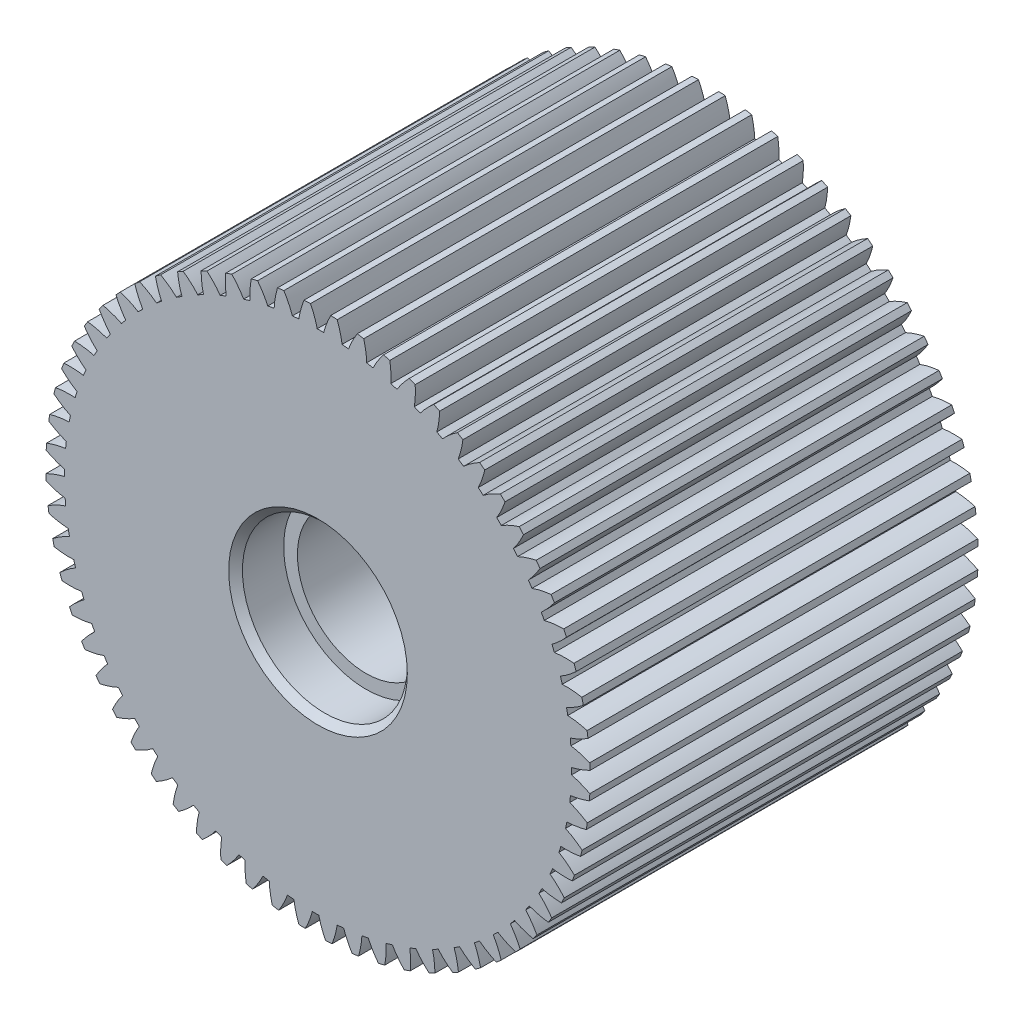
SolidWorks part; units mm, degrees
material "PLA"
ref_plane "Front Plane" through (0, 0, 0) normal (0, 0, 1) x (1, 0, 0)
ref_plane "Top Plane" through (0, 0, 0) normal (0, 1, 0) x (1, 0, 0)
ref_plane "Right Plane" through (0, 0, 0) normal (1, 0, 0) x (0, 0, -1)
sketch "Sketch1" plane through (0, 0, 0) normal (0, 0, 1) x (1, 0, 0)
  circle A0 centre (0, 0) radius 19.8
  dimension "D1" = 39.6
extrude "Boss-Extrude1" add sketch "Sketch1" along normal mid plane 28.2315
sketch "Sketch2" plane through (0, 0, 0) normal (0, 0, 1) x (1, 0, 0)
  line L0 (0, 0) -> (18.0421, 0) construction
  line L1 (0, 0) -> (19.1991, -0.1851) construction
  line L2 (0, 0) -> (18.0387, -0.3478) construction
  line L3 (18.0421, 0) -> (18.45, 0)
  line L4 (18.0387, -0.3478) -> (18.4466, -0.3557)
  circle A0 centre (0, 0) radius 19.2 construction
  circle A1 centre (0, 0) radius 18.0421 construction
  circle A2 centre (0, 0) radius 18.45
  circle A3 centre (0, 0) radius 19.8 construction
  circle A4 centre (0, 0) radius 19.8
  spline S0 degree 4 poles (18.0421, 0) (18.0483, 0.0001) (18.0656, 0.0006) (18.0982, 0.0027) (18.1515, 0.0076) (18.2192, 0.0162) (18.3065, 0.0298) (18.409, 0.0492) (18.5213, 0.0739) (18.643, 0.1046) (18.7639, 0.1385) (18.8839, 0.1754) (19.0031, 0.215) (19.1468, 0.2661) (19.3181, 0.3318) (19.517, 0.4152) (19.7406, 0.5174) (19.9664, 0.6297) (20.1868, 0.7469) (20.4071, 0.8728) (20.6187, 1) (20.8359, 1.1397) (21.0351, 1.2726) (21.2552, 1.4299) (21.432, 1.5592) (21.6617, 1.7386) (21.7964, 1.8472) (21.9527, 1.9772) (22.0215, 2.0366) (22.0639, 2.0731) knots 0 0 0 0 0 0.005377 0.015084 0.028532 0.04661 0.064855 0.092111 0.119476 0.146842 0.174209 0.201575 0.228941 0.256307 0.307035 0.361767 0.4165 0.471232 0.525964 0.580697 0.635429 0.690161 0.744894 0.799626 0.854358 0.909091 0.954545 1 1 1 1 1 construction
  spline S1 degree 4 poles (18.0421, 0) (18.0483, 0.0001) (18.0656, 0.0006) (18.0982, 0.0027) (18.1515, 0.0076) (18.2192, 0.0162) (18.3065, 0.0298) (18.409, 0.0492) (18.5213, 0.0739) (18.643, 0.1046) (18.7639, 0.1385) (18.8839, 0.1754) (19.0031, 0.215) (19.1468, 0.2661) (19.3181, 0.3318) (19.517, 0.4152) (19.7406, 0.5174) (19.9664, 0.6297) (20.1868, 0.7469) (20.4071, 0.8728) (20.6187, 1) (20.8359, 1.1397) (21.0351, 1.2726) (21.2552, 1.4299) (21.432, 1.5592) (21.6119, 1.6997) (21.6991, 1.7691) (21.7435, 1.805) knots 0 0 0 0 0 0.005377 0.015084 0.028532 0.04661 0.064855 0.092111 0.119476 0.146842 0.174209 0.201575 0.228941 0.256307 0.307035 0.361767 0.4165 0.471232 0.525964 0.580697 0.635429 0.690161 0.744894 0.799626 0.854358 0.909091 0.909091 0.909091 0.909091 0.909091
  spline S2 degree 4 poles (18.0387, -0.3478) (18.0449, -0.348) (18.0622, -0.3489) (18.0948, -0.3516) (18.148, -0.3575) (18.2155, -0.3674) (18.3025, -0.3827) (18.4047, -0.404) (18.5164, -0.431) (18.6375, -0.464) (18.7577, -0.5002) (18.8771, -0.5394) (18.9954, -0.5812) (19.1381, -0.6351) (19.3081, -0.7042) (19.5053, -0.7914) (19.727, -0.8979) (19.9506, -1.0145) (20.1686, -1.1359) (20.3865, -1.266) (20.5956, -1.3973) (20.8101, -1.5412) (21.0066, -1.6779) (21.2237, -1.8393) (21.3979, -1.9721) (21.6242, -2.1559) (21.7567, -2.267) (21.9105, -2.4001) (21.9782, -2.4607) (22.0198, -2.498) knots 0 0 0 0 0 0.005377 0.015084 0.028532 0.04661 0.064855 0.092111 0.119476 0.146842 0.174209 0.201575 0.228941 0.256307 0.307035 0.361767 0.4165 0.471232 0.525964 0.580697 0.635429 0.690161 0.744894 0.799626 0.854358 0.909091 0.954545 1 1 1 1 1 construction
  spline S3 degree 4 poles (18.0387, -0.3478) (18.0449, -0.348) (18.0622, -0.3489) (18.0948, -0.3516) (18.148, -0.3575) (18.2155, -0.3674) (18.3025, -0.3827) (18.4047, -0.404) (18.5164, -0.431) (18.6375, -0.464) (18.7577, -0.5002) (18.8771, -0.5394) (18.9954, -0.5812) (19.1381, -0.6351) (19.3081, -0.7042) (19.5053, -0.7914) (19.727, -0.8979) (19.9506, -1.0145) (20.1686, -1.1359) (20.3865, -1.266) (20.5956, -1.3973) (20.8101, -1.5412) (21.0066, -1.6779) (21.2237, -1.8393) (21.3979, -1.9721) (21.5751, -2.116) (21.661, -2.1871) (21.7046, -2.2238) knots 0 0 0 0 0 0.005377 0.015084 0.028532 0.04661 0.064855 0.092111 0.119476 0.146842 0.174209 0.201575 0.228941 0.256307 0.307035 0.361767 0.4165 0.471232 0.525964 0.580697 0.635429 0.690161 0.744894 0.799626 0.854358 0.909091 0.909091 0.909091 0.909091 0.909091
  dimension "D1" = 38.4
  dimension "D2" = 36.0842
  dimension "D3" = 36.9
  dimension "D4" = 0.552
  dimension "D5" = 0.552
extrude "Cut-Extrude1" cut sketch "Sketch2" against normal through all both and the other way through all contours A2 S3 A4 S1 region at (19.2453, -0.1855, 0)
pattern_circular "CirPattern2" count 64 over 360 about axis through (0, 0, -14.1158) along (0, 0, 1) of "Cut-Extrude1"
sketch "Sketch3" plane through (0, 0, 14.1158) normal (0, 0, 1) x (1, 0, 0)
  circle A0 centre (0, 0) radius 5
  dimension "D1" = 10
extrude "Cut-Extrude2" cut sketch "Sketch3" against normal through all both and the other way through all
sketch "Sketch4" plane through (0, 0, 14.1158) normal (0, 0, 1) x (1, 0, 0)
  circle A0 centre (0, 0) radius 6
  dimension "D1" = 12
extrude "Cut-Extrude3" cut sketch "Sketch4" against normal blind 3.5 contours A0
mirror "Mirror2" about plane through (0, 0, 0) normal (0, 0, 1) of "Cut-Extrude3"
chamfer "Chamfer1" distance 0.5 angle 45 2 edges at (6, 0, 14.1158) (6, 0, -14.1158)
equation "\"Ns\" = 48"
equation "\"module\" = 0.6"
equation "\"pressure angle\" = 20.0"
equation "\"h_a\" = 0.6"
equation "\"h_b\" = 0.75"
equation "\"clr_tip_root\" = 0.15000000000000002"
equation "\"dp_s\" = 28.799999999999997"
equation "\"db_s\" = 27.06314747863416"
equation "\"D1@Sketch1\"=\"dp_fs\" + 2*\"h_a\""
equation "\"fw_s_calc\" = 7.664359769718526"
equation "\"D1@Boss-Extrude1\"=\"fw_fs\"-2mm"
equation "\"D1@Sketch2\"=\"dp_fs\""
equation "\"D2@Sketch2\"=\"db_fs\""
equation "\"D3@Sketch2\"=\"dp_fs\"- 2*\"h_b\""
equation "\"alpha_s\" = 0.8539582918412343"
equation "\"D4@Sketch2\"=\"beta_fs\"/2"
equation "\"beta_s\" = 2.0420834163175314"
equation "\"D5@Sketch2\"=\"beta_fs\"/2"
equation "\"D1@CirPattern2\"=\"Ns_fs\""
equation "\"pressure_angle\" = 20.0"
equation "\"h_f\" = 0.75"
equation "\"bearing_ID\" = 65"
equation "\"bearing_OD\" = 85"
equation "\"bearing_height\" = 10"
equation "\"clearance_planet\" = 1.5"
equation "\"case_dist\" = 6.5"
equation "\"Motor_case_OD_max\" = 131.3"
equation "\"case_mounting_PCD\" = 123.8"
equation "\"bearing mount thickness\" = 8"
equation "\"case_mounting_hole_dia\" = 3"
equation "\"output_mounting_PCD\" = 93"
equation "\"output_mounting_hole_dia\" = 4"
equation "\"clearance_case_mount_holes_shell_thickness\" = 1"
equation "\"motor_case_OD_base\" = 121.8"
equation "\"sec_carrier_thickness\" = 5"
equation "\"sun_coupler_hub_thickness\" = 4"
equation "\"clearance_sun_coupler_sec_carrier\" = 1.5"
equation "\"clearance_motor_and_case\" = 5"
equation "\"motor_OD\" = 106.8"
equation "\"Motor_case_thickness\" = 2.5"
equation "\"Motor_case_ID\" = 116.8"
equation "\"case_mounting_hole_shift\" = 1.0"
equation "\"output_mounting_nut_wrench_size\" = 7"
equation "\"output_mounting_nut_thickness\" = 3.2"
equation "\"case_mounting_hole_allen_socket_dia\" = 5.5"
equation "\"output_mounting_nut_depth\" = 3"
equation "\"case_mounting_bolt_depth\" = 4.5"
equation "\"ring_radial_thickness\" = 5"
equation "\"ring_to_chamfer_clearance\" = 1.5"
equation "\"Motor_case_OD_base_to_chamfer\" = 5"
equation "\"pattern_offset_from_motor_case_OD_base\" = 3"
equation "\"pattern_bulge_dia\" = 3"
equation "\"pattern_num_bulge\" = 18"
equation "\"pattern_depth\" = 2"
equation "\"motor_height\" = 47.6"
equation "\"case_mounting_wrench_size\" = 5.5"
equation "\"case_mounting_nut_clearance\" = 2"
equation "\"base_plate_thickness\" = 4"
equation "\"case_mounting_nut_thickness\" = 2.4"
equation "\"case_mounting_surface_height\" = 4"
equation "\"motor_mount_hole_PCD\" = 40"
equation "\"motor_mount_hole_dia\" = 5"
equation "\"motor_mount_hole_num\" = 4"
equation "\"central_hole_offset_from_motor_mount_PCD\" = 5"
equation "\"wire_slot_dist_from_center\" = 45.5"
equation "\"wire_slot_length\" = 10"
equation "\"wire_slot_radius\" = 3"
equation "\"driver_upper_holes_dist_from_center\" = 29"
equation "\"driver_lower_holes_dist_from_center\" = 13"
equation "\"driver_side_holes_dist_from_center\" = 22.5"
equation "\"driver_mount_holes_dia\" = 3"
equation "\"driver_mount_inserts_OD\" = 4.8"
equation "\"driver_mount_thickness\" = 1.5"
equation "\"driver_mount_height\" = 6"
equation "\"air_flow_hole_offset\" = 3"
equation "\"num_planet\" = 4"
equation "\"planet_pin_bolt_dia\" = 5"
equation "\"planet_pin_socket_head_dia\" = 8.5"
equation "\"carrier_PCD\" = 57.599999999999994"
equation "\"planet_shaft_dia\" = 8"
equation "\"planet_shaft_step_offset\" = 1"
equation "\"carrier_trapezoidal_support_sun_offset\" = 5"
equation "\"carrier_trapezoidal_support_hole_PCD_offset_bearing_ID\" = 4"
equation "\"carrier_trapezoidal_support_hole_dia\" = 3"
equation "\"carrier_trapezoidal_support_hole_socket_head_dia\" = 5.5"
equation "\"carrier_bearing_step_width\" = 1.5"
equation "\"standard_clearance_1_5mm\" = 1.5"
equation "\"standard_fillet_1_5mm\" = 1.5"
equation "\"sun_shaft_bearing_OD\" = 16"
equation "\"sun_shaft_bearing_width\" = 5"
equation "\"standard_bearing_insertion_chamfer\" = 0.5"
equation "\"carrier_trapezoidal_support_hole_wrench_size\" = 5.5"
equation "\"planet_pin_bolt_wrench_size\" = 8"
equation "\"planet_bearing_OD\" = 12"
equation "\"planet_bearing_width\" = 3.5"
equation "\"planet_bore\" = 10"
equation "\"motor_output_hole_PCD\" = 23"
equation "\"motor_output_hole_dia\" = 4"
equation "\"motor_output_hole_num\" = 4"
equation "\"sun_shaft_bearing_ID\" = 8"
equation "\"sun_hub_dia\" = 30.0"
equation "\"sun_central_bolt_dia\" = 5"
equation "\"sun_central_bolt_socket_head_dia\" = 8.5"
equation "\"fw_s_used\" = 72.54334182621932"
equation "\"motor_output_hole_CSK_OD\" = 8"
equation "\"motor_output_hole_CSK_head_height\" = 2.0"
equation "\"Np_b\" = 48"
equation "\"dp_p_b\" = 28.799999999999997"
equation "\"db_p_b\" = 27.06314747863416"
equation "\"fw_p_s\" = 30.231545005724083"
equation "\"alpha_p_b\" = 0.8539582918412343"
equation "\"beta_p_b\" = 2.0420834163175314"
equation "\"bearing_retainer_thickness\" = 2"
equation "\"Np_s\" = 32"
equation "\"fw_p_b\" = 34.81179682049524"
equation "\"dp_p_s\" = 19.2"
equation "\"db_p_s\" = 18.04209831908944"
equation "\"alpha_p_s\" = 0.8539582918412556"
equation "\"beta_p_s\" = 3.917083416317489"
equation "\"Cut-Extrude9\"= IIF ( ( \"Ns\" * \"module\" + 2 * \"h_a\" ) < ( \"motor_output_hole_PCD\" - \"motor_output_hole_CSK_OD\" ) , \"suppressed\" , \"unsuppressed\" )"
equation "\"Nr_b\" = 144"
equation "\"dp_r_b\" = 86.39999999999999"
equation "\"db_r_b\" = 81.18944243590248"
equation "\"fw_r_b\" = 34.81179682049524"
equation "\"alpha_r_b\" = 0.8539582918412414"
equation "\"beta_r_b\" = 2.957916583682483"
equation "\"ring_OD_b\" = 96.39999999999999"
equation "\"Fillet10\"= IIF ( \"ring_OD_b\" > ( \"bearing_OD\" + 2 * \"bearing mount thickness\" ) , \"suppressed\" , \"unsuppressed\" )"
equation "\"Fillet11\"= IIF ( \"ring_OD_b\" < ( \"bearing_OD\" + 2 * \"bearing mount thickness\" ) , \"suppressed\" , \"unsuppressed\" )"
equation "\"Nr_s\" = 128"
equation "\"clr_tip_root_s\" = 0.15000000000000002"
equation "\"dp_r_s\" = 76.8"
equation "\"db_r_s\" = 72.16839327635776"
equation "\"fw_r_s\" = 28.731545005724083"
equation "\"alpha_r_s\" = 0.8539582918412556"
equation "\"beta_r_s\" = 3.114166583682511"
equation "\"small_ring_case_thickness\" = 4"
equation "\"carrier_thickness\" = 4"
equation "\"small_ring_output_wall_thickness\" = 5"
equation "\"small_ring_output_wall_to_bearing_shaft_attachement_hole_dia\" = 4"
equation "\"small_ring_output_wall_to_bearing_shaft_attachement_hole_depth\" = 6.5"
equation "\"small_ring_output_wall_to_bearing_shaft_attachement_nut_wrench\" = 7"
equation "\"small_ring_output_wall_to_bearing_shaft_attachement_nut_thickness\" = 3.2"
equation "\"small_ring_output_wall_to_bearing_shaft_attachement_hole_pcd\" = 12"
equation "\"small_ring_output_wall_to_bearing_shaft_attachement_hole_num\" = 3"
equation "\"small_ring_output_wall_to_bearing_shaft_attachement_hole_CSK_OD\" = 8"
equation "\"small_ring_output_wall_to_bearing_shaft_attachement_hole_CSK_head_height\" = 2.0"
equation "\"carrier_small_ring_inner_bearing_ID\" = 20"
equation "\"carrier_small_ring_inner_bearing_OD\" = 32"
equation "\"carrier_small_ring_inner_bearing_height\" = 7"
equation "\"carrier_small_ring_inner_bearing_flap\" = 2"
equation "\"gear_casing_big_ring_to_bearing_dist\" = 39.23154500572409"
equation "\"gear_casing_thickness\" = 4"
equation "\"tight_clearance_3DP\" = 0.4"
equation "\"loose_clearance_3DP\" = 0.8"
equation "\"Cut-Extrude10\"= IIF ( ( \"Ns\" * \"module\" - 2 * \"h_a\" ) < ( \"motor_output_hole_PCD\" + \"motor_output_hole_dia\" + \"standard_clearance_1_5mm\" * 4 / 3 ) , \"suppressed\" , \"unsuppressed\" )"
equation "\"Ns_fs\" = 64"
equation "\"dp_fs\" = 38.4"
equation "\"db_fs\" = 36.08419663817888"
equation "\"alpha_fs\" = 0.8539582918412556"
equation "\"beta_fs\" = 1.1045834163174888"
equation "\"fw_fs\" = 30.231545005724083"
equation "\"num_idler\" = 4"
equation "\"idler_angle_offset\" = 45.0"
equation "\"fs_bore_dia\" = 31.599999999999998"
equation "\"fs_bore_wall\" = 2.6500000000000004"
equation "\"fs_axial_clearance\" = 0.8"
equation "\"D1@Sketch3\"=\"planet_bore\""
equation "\"D1@Sketch4\"=\"planet_bearing_OD\""
equation "\"D1@Cut-Extrude3\"=\"planet_bearing_width\""
equation "\"D1@Chamfer1\"=\"standard_bearing_insertion_chamfer\""
